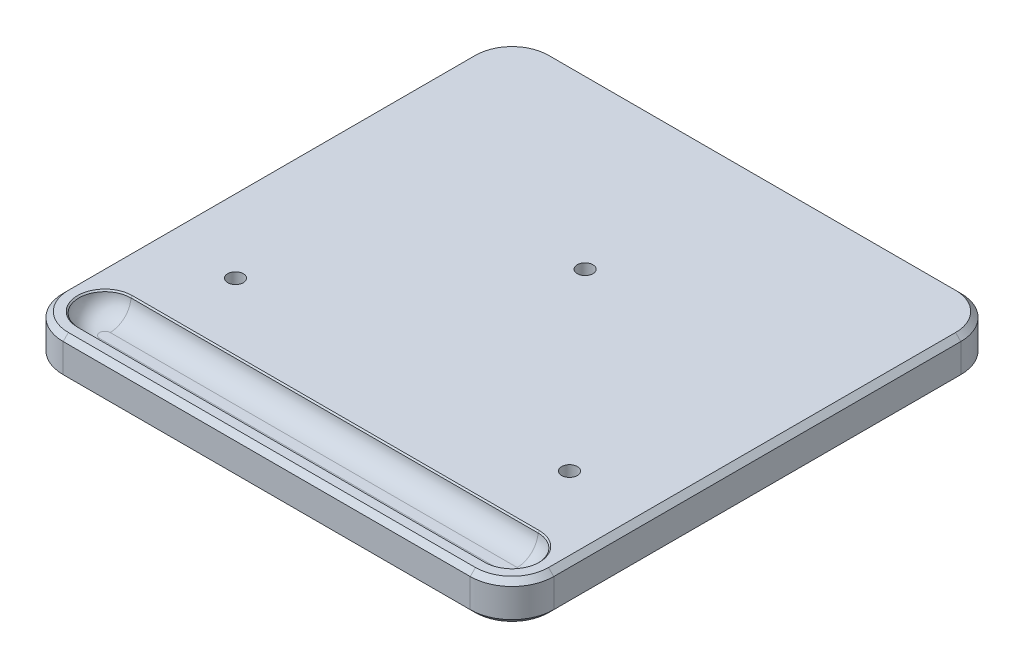
SolidWorks part; units mm, degrees
note: '?' marks a value the reader was unsure of.
ref_plane "Front Plane" through (0, 0, 0) normal (0, 0, 1) x (1, 0, 0)
ref_plane "Top Plane" through (0, 0, 0) normal (0, 1, 0) x (1, 0, 0)
ref_plane "Right Plane" through (0, 0, 0) normal (1, 0, 0) x (0, 0, -1)
sketch "Sketch1" plane through (0, 0, 0) normal (0, 1, 0) x (1, 0, 0)
  line L1 (-76.2, -76.2) -> (76.2, -76.2) construction
  line L2 (-76.2, -76.2) -> (-76.2, 76.2) construction
  line L3 (-76.2, 76.2) -> (76.2, 76.2) construction
  line L4 (76.2, -76.2) -> (76.2, 76.2) construction
  line L5 (-76.2, -76.2) -> (76.2, 76.2) construction
  line L6 (-76.2, 76.2) -> (76.2, -76.2) construction
  point P0 (0, 0)
  dimension "Length" = 152.4
  dimension "Width" = 152.4
sketch "Sketch2" plane through (0, 0, 0) normal (1, 0, 0) x (0, 0, -1)
  line L1 (-76.2, -5.9531) -> (76.2, -5.9531) construction
  line L2 (-76.2, -5.9531) -> (-76.2, 5.9531) construction
  line L3 (-76.2, 5.9531) -> (76.2, 5.9531) construction
  line L4 (76.2, -5.9531) -> (76.2, 5.9531) construction
  line L5 (-76.2, -5.9531) -> (76.2, 5.9531) construction
  line L6 (-76.2, 5.9531) -> (76.2, -5.9531) construction
  dimension "Thickness" = 11.9062
sketch "Sketch3" plane through (0, 0, 0) normal (1, 0, 0) x (0, 0, -1)
  line L1 (76.2, 5.9531) -> (-76.2, 5.9531)
  line L2 (76.2, 5.9531) -> (76.2, -5.9531)
  line L3 (76.2, -5.9531) -> (-76.2, -5.9531)
  line L4 (-76.2, 5.9531) -> (-76.2, -5.9531)
extrude "Boss-Extrude1" add sketch "Sketch3" against normal up to vertex (76.2 mm away) and the other way up to vertex (76.2 mm away) up to point (-76.2, 0, -76.2) other way up to point (76.2, 0, -76.2)
sketch "Sketch8" plane through (0, -5.9531, 0) normal (0, -1, 0) x (1, 0, 0)
  line L8 (-74.6125, -74.6125) -> (74.6125, -74.6125)
  line L9 (74.6125, -74.6125) -> (74.6125, 74.6125)
  line L10 (74.6125, 74.6125) -> (-74.6125, 74.6125)
  line L11 (-74.6125, 74.6125) -> (-74.6125, -74.6125)
  line L12 (-61.9125, -74.6125) -> (61.9125, -74.6125)
  line L13 (74.6125, -61.9125) -> (74.6125, 61.9125)
  line L14 (61.9125, 74.6125) -> (-61.9125, 74.6125)
  line L15 (-74.6125, 61.9125) -> (-74.6125, -61.9125)
  arc A0 (-61.9125, -74.6125) -> (-74.6125, -61.9125) centre (-61.9125, -61.9125) cw
  arc A1 (61.9125, -74.6125) -> (74.6125, -61.9125) centre (61.9125, -61.9125) ccw
  arc A2 (74.6125, 61.9125) -> (61.9125, 74.6125) centre (61.9125, 61.9125) ccw
  arc A3 (-61.9125, 74.6125) -> (-74.6125, 61.9125) centre (-61.9125, 61.9125) ccw
  dimension "D2" = 12.7
  dimension "D1" = 1.5875
extrude "Cut-Extrude2" cut sketch "Sketch8" against normal through all flip side to cut
chamfer "Chamfer1" distance 1.5875 angle 45 16 edges at (-74.6125, -5.9531, 0) (-70.8928, -5.9531, -70.8928) (-70.8928, -5.9531, 70.8928) (0, -5.9531, -74.6125) (0, -5.9531, 74.6125) (70.8928, -5.9531, -70.8928) (70.8928, -5.9531, 70.8928) (74.6125, -5.9531, 0) (-74.6125, 5.9531, 0) (-70.8928, 5.9531, -70.8928) (-70.8928, 5.9531, 70.8928) (0, 5.9531, -74.6125) (0, 5.9531, 74.6125) (70.8928, 5.9531, -70.8928) (70.8928, 5.9531, 70.8928) (74.6125, 5.9531, 0)
sketch "Pen Slot Sketch" plane through (0, 5.9531, 0) normal (0, 1, 0) x (1, 0, 0)
  line L0 (-61.9125, -61.9125) -> (61.9125, -61.9125) construction
  line L1 (-61.9125, -53.975) -> (61.9125, -53.975)
  line L2 (-61.9125, -69.85) -> (61.9125, -69.85)
  line L3 (73.025, -61.9125) -> (73.025, 61.9125) construction
  line L5 (-73.025, 61.9125) -> (-73.025, -61.9125) construction
  line L6 (-61.9125, -73.025) -> (61.9125, -73.025) construction
  arc A0 (-61.9125, -53.975) -> (-61.9125, -69.85) centre (-61.9125, -61.9125) ccw
  arc A1 (61.9125, -69.85) -> (61.9125, -53.975) centre (61.9125, -61.9125) ccw
  point P2 (0, -61.9125)
  point P9 (-69.85, -61.9125)
  point P12 (69.85, -61.9125)
  dimension "D2" = 3.175
  dimension "D3" = 3.175
  dimension "D4" = 3.175
extrude "Pen Slot Cut" cut sketch "Pen Slot Sketch" against normal blind 6.35
fillet "Pen Slot Fillet" radius 6.35 4 edges at (0, -0.3969, 53.975) (69.85, -0.3969, 61.9125) (0, -0.3969, 69.85) (-69.85, -0.3969, 61.9125)
sketch "Sketch4" plane through (0, -5.9531, 0) normal (0, -1, 0) x (1, 0, 0)
  line L0 (-50.8, 33.3078) -> (50.8, 33.3078) construction
  line L1 (-50.8, 33.3078) -> (-50.8, -74.6125) construction
  line L2 (50.8, 33.3078) -> (50.8, -74.6125) construction
  line L3 (-50.8, -74.6125) -> (50.8, -74.6125) construction
  line L5 (-61.9125, -74.6125) -> (61.9125, -74.6125) construction
  point P0 (-50.8, 33.3078)
  point P1 (50.8, 33.3078)
  point P3 (0, -22.2235)
hole_wizard "Hole1" positions "3DSketch1" profile "Sketch5" legacy end condition through all
sketch3d "3DSketch1"
  point P0 (-50.8, -5.9531, 33.3078)
  point P3 (50.8, -5.9531, 33.3078)
  point P6 (0, -5.9531, -22.2235)
sketch "Sketch5" plane through (-50.8, -5.9531, 33.3078) normal (1, 0, 0) x (0, 0, -1)
  line L0 (0, 0) -> (0, 11.9062)
  line L1 (0, 11.9062) -> (2.3812, 11.9062)
  line L3 (2.3812, 11.9062) -> (2.3812, 6.35)
  line L4 (2.3812, 6.35) -> (6.35, 6.35)
  line L5 (6.35, 6.35) -> (6.35, 0)
  line L7 (6.35, 0) -> (0, 0)
  line L11 (0, -6.35) -> (0, 107.95) construction
  dimension "Thru Hole Dia." = 4.7625
  dimension "Thru Hole Depth" = 11.9062
  dimension "C'Bore Dia." = 12.7
  dimension "C'Bore Depth" = 6.35
sketch "Sketch6" plane through (0, -5.9531, 0) normal (0, -1, 0) x (-1, 0, 0)
  line L0 (74.6125, -61.9125) -> (74.6125, 61.9125) construction
  line L1 (61.9125, 61.9125) -> (-61.9125, 61.9125) construction
  line L2 (61.9125, 61.9125) -> (61.9125, -61.9125) construction
  line L3 (61.9125, -61.9125) -> (-61.9125, -61.9125) construction
  line L4 (-61.9125, 61.9125) -> (-61.9125, -61.9125) construction
  line L5 (61.9125, 61.9125) -> (-61.9125, -61.9125) construction
  line L6 (61.9125, -61.9125) -> (-61.9125, 61.9125) construction
  circle A0 centre (-61.9125, 61.9125) radius 6.7469
  circle A1 centre (61.9125, 61.9125) radius 6.7469
  circle A2 centre (61.9125, -61.9125) radius 6.7469
  circle A3 centre (-61.9125, -61.9125) radius 6.7469
  point P0 (0, 0)
  dimension "D2" = 13.4937
  dimension "D1" = 12.7
extrude "Cut-Extrude1" cut sketch "Sketch6" against normal blind 1.524
chamfer "Chamfer2" distance 0.3969 angle 45 8 edges at (0, 5.9531, 53.975) (-69.85, 5.9531, 61.9125) (69.85, 5.9531, 61.9125) (0, 5.9531, 69.85) (61.9125, -5.9531, 55.1656) (-61.9125, -5.9531, 55.1656) (-61.9125, -5.9531, -68.6594) (61.9125, -5.9531, -68.6594)
chamfer "Base Chamfers" distance 0.7937 angle 45 3 edges at (50.8, -5.9531, 26.9578) (-50.8, -5.9531, 26.9578) (0, -5.9531, -28.5735)
ref_axis "Axis1" through (0, 0, 0) along (0, 1, 0)?
